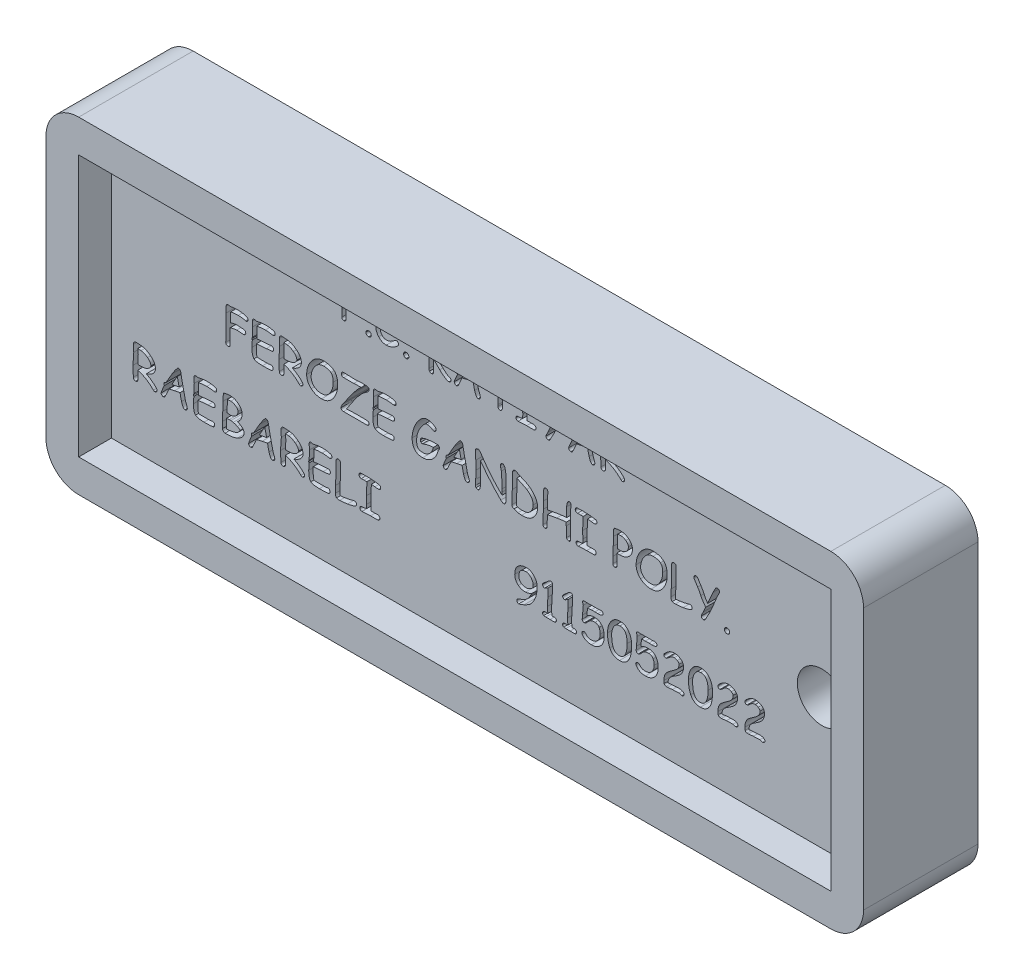
SolidWorks part; units mm, degrees
ref_plane "Front Plane" through (0, 0, 0) normal (0, 0, 1) x (1, 0, 0)
ref_plane "Top Plane" through (0, 0, 0) normal (0, 1, 0) x (1, 0, 0)
ref_plane "Right Plane" through (0, 0, 0) normal (1, 0, 0) x (0, 0, -1)
sketch "Sketch1" plane through (0, 0, 0) normal (0, 0, 1) x (1, 0, 0)
  line L1 (-23, -10) -> (23, -10)
  line L2 (-25, -8) -> (-25, 8)
  line L3 (-23, 10) -> (23, 10)
  line L4 (25, -8) -> (25, 8)
  line L5 (-25, -10) -> (25, 10) construction
  line L6 (-25, 10) -> (25, -10) construction
  line L11 (-21.25, -6.125) -> (21.25, 6.125) construction
  line L12 (-21.25, 6.125) -> (21.25, -6.125) construction
  arc A0 (-23, -10) -> (-25, -8) centre (-23, -8) cw
  arc A1 (25, -8) -> (23, -10) centre (23, -8) cw
  arc A2 (25, 8) -> (23, 10) centre (23, 8) ccw
  arc A3 (-23, 10) -> (-25, 8) centre (-23, 8) ccw
  point P0 (0, 0)
  point P5 (0, 0)
  dimension "D3" = 2
  dimension "D1" = 50
  dimension "D2" = 20
extrude "Boss-Extrude2" add sketch "Sketch1" against normal blind 7
sketch "Sketch2" plane through (0, 0, 0) normal (0, 0, 1) x (1, 0, 0)
  line L0 (-25, 8) -> (-25, -8) construction
  line L1 (-23, -8) -> (23, -8)
  line L2 (-23, -8) -> (-23, 8)
  line L3 (-23, 8) -> (23, 8)
  line L4 (23, -8) -> (23, 8)
  line L5 (-23, -8) -> (23, 8) construction
  line L6 (-23, 8) -> (23, -8) construction
  line L7 (23, 10) -> (-23, 10) construction
  point P0 (0, 0)
  dimension "D1" = 2
  dimension "D2" = 2
extrude "Cut-Extrude1" cut sketch "Sketch2" against normal blind 2
sketch "Sketch3" plane through (0, 0, -7) normal (0, 0, -1) x (-1, 0, 0)
  line L0 (-25, -8) -> (-25, 8) construction
  line L1 (-23, -8) -> (23, -8)
  line L2 (-23, -8) -> (-23, 8)
  line L3 (-23, 8) -> (23, 8)
  line L4 (23, -8) -> (23, 8)
  line L5 (-23, -8) -> (23, 8) construction
  line L6 (-23, 8) -> (23, -8) construction
  line L7 (-23, 10) -> (23, 10) construction
  point P0 (0, 0)
  dimension "D1" = 2
  dimension "D2" = 2
extrude "Cut-Extrude2" cut sketch "Sketch3" against normal blind 2
sketch "Sketch4" plane through (0, 0, -2) normal (0, 0, 1) x (1, 0, 0)
  circle A0 centre (20.4509, 0) radius 1.5
  dimension "D1" = 3
extrude "Cut-Extrude3" cut sketch "Sketch4" against normal blind 3
sketch "Sketch5" plane through (0, 0, -2) normal (0, 0, 1) x (1, 0, 0)
  text T0 "                P.C. KATIYAR\r\n       FEROZE GANDHI POLY.\r\nRAEBARELI          9115052022" font "Comic Sans MS" height 2
extrude "Cut-Extrude4" cut sketch "Sketch5" against normal blind 3
